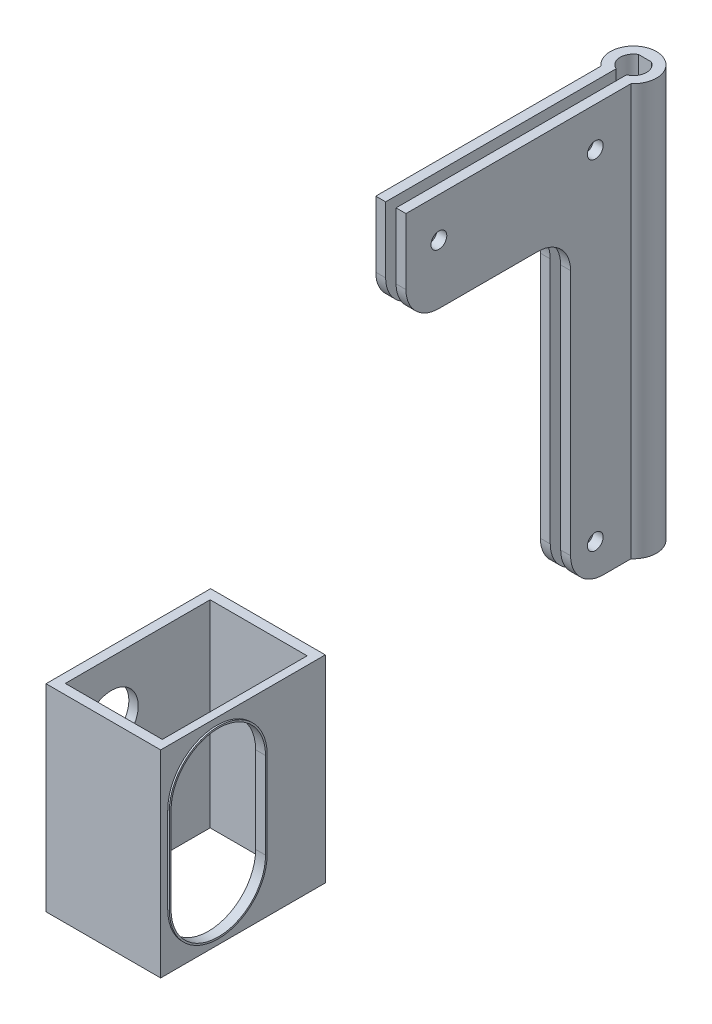
SolidWorks part; units mm, degrees
ref_plane "Front Plane" through (0, 0, 0) normal (0, 0, 1) x (1, 0, 0)
ref_plane "Top Plane" through (0, 0, 0) normal (0, 1, 0) x (1, 0, 0)
ref_plane "Right Plane" through (0, 0, 0) normal (1, 0, 0) x (0, 0, -1)
ref_plane "ULTRASONIC CENTER" through (0, 0, 125) normal (0, 0, 1) x (1, 0, 0)
sketch "Sketch1" plane through (0, 0, 0) normal (0, 1, 0) x (1, 0, 0)
  line L0 (-1.5875, -3.6715) -> (-1.5875, -23.6715)
  line L1 (1.5875, -3.6715) -> (1.5875, -23.6715)
  line L2 (1.9365, 3.5) -> (-1.9365, 3.5)
  line L3 (4.5875, -5.2872) -> (4.5875, -23.6715)
  line L4 (-4.5875, -5.2872) -> (-4.5875, -23.6715)
  line L5 (-4.5875, -23.6715) -> (-1.5875, -23.6715)
  line L6 (1.5875, -23.6715) -> (4.5875, -23.6715)
  arc A0 (1.5875, -3.6715) -> (1.9365, 3.5) centre (0, 0) ccw
  arc A1 (4.5875, -5.2872) -> (-4.5875, -5.2872) centre (0, 0) ccw
  arc A2 (-1.9365, 3.5) -> (-1.5875, -3.6715) centre (0, 0) ccw
  arc A4 (1.5875, -3.6715) -> (-1.5875, -3.6715) centre (0, 0) ccw construction
  dimension "D1" = 4
  dimension "D2" = 20
  dimension "D3" = 3.5
  dimension "D5" = 3.175
  dimension "D4" = 3
extrude "Boss-Extrude1" add sketch "Sketch1" along normal blind 125
ref_plane "PADDLE CENTER" through (0, 0, 0) normal (-1, 0, 0) x (0, 0, 1)
ref_plane "DISC CENTER" through (0, -15, 0) normal (0, 1, 0) x (1, 0, 0)
ref_axis "Axis1" through (0, -15, 24.6715) along (0, 0, -1)
ref_plane "OFFSET" through (-36.4125, 0, 0) normal (-1, 0, 0) x (0, 0, 1)
ref_plane "PADDLE SURFACE" through (-1.5875, 0, 0) normal (1, 0, 0) x (0, 0, -1)
ref_axis "Axis2" through (-36.4125, -15, -8.5336) along (0, 0, 1)
ref_point "ULTRASONIC"
sketch "Sketch5" plane through (0, 125, 0) normal (0, 1, 0) x (1, 0, 0)
  line L1 (-1.5875, -111.5) -> (-1.5875, -106.5)
  line L2 (-47.5875, -106.5) -> (-47.5875, -141.5)
  line L3 (-47.5875, -141.5) -> (-1.5875, -141.5)
  line L4 (-1.5875, -141.5) -> (-1.5875, -136.5)
  line L5 (-1.5875, -136.5) -> (-42.5875, -136.5)
  line L9 (-1.5875, -23.6715) -> (-1.5875, -3.6715) construction
  line L10 (-42.5875, -111.5) -> (-1.5875, -111.5)
  line L12 (-42.5875, -136.5) -> (-42.5875, -111.5)
  line L13 (-47.5875, -106.5) -> (-1.5875, -106.5)
  line L18 (-18.6703, -4) -> (17.7565, -4) construction
  circle A0 centre (0, 0) radius 4 construction
  arc A1 (-1.9365, 3.5) -> (-1.5875, -3.6715) centre (0, 0) ccw construction
  point P2 (-42.5875, -124)
  dimension "D2" = 120
  dimension "D1" = 41
  dimension "D3" = 25
  dimension "D4" = 5
  dimension "D5" = 5
  dimension "D7" = 5
extrude "Boss-Extrude2" [suppressed] add sketch "Sketch5" against normal mid plane 30 from offset 137.5 offset against normal yes
sketch "Sketch6" plane through (0, 125, 0) normal (0, 1, 0) x (1, 0, 0)
  line L0 (4.5875, -23.6715) -> (4.5875, -5.2872) construction
  line L1 (1.5875, -23.6715) -> (4.5875, -23.6715)
  line L2 (1.5875, -23.6715) -> (1.5875, -73.6715)
  line L3 (1.5875, -73.6715) -> (4.5875, -73.6715)
  line L4 (4.5875, -23.6715) -> (4.5875, -73.6715)
  line L6 (-1.5875, -23.6715) -> (-1.5875, -3.6715) construction
  line L7 (-4.5875, -23.6715) -> (-1.5875, -23.6715)
  line L8 (-4.5875, -23.6715) -> (-4.5875, -73.6715)
  line L9 (-4.5875, -73.6715) -> (-1.5875, -73.6715)
  line L10 (-1.5875, -23.6715) -> (-1.5875, -73.6715)
  dimension "D1" = 50
extrude "Boss-Extrude3" add sketch "Sketch6" against normal blind 30
fillet "Fillet6" radius 10 6 edges at (3.0875, 0, 23.6715) (-3.0875, 0, 23.6715) (3.0875, 95, 73.6715) (-3.0875, 95, 73.6715) (3.0875, 95, 23.6715) (-3.0875, 95, 23.6715)
hole_wizard "M4 Clearance Hole1" positions "Sketch2" profile "Sketch3" hole size "M4" standard "ANSI Metric" end condition through all
sketch "Sketch2" plane through (4.5875, 0, 0) normal (1, 0, 0) x (0, 0, -1)
  line L4 (-73.6715, 125) -> (-5.2872, 125) construction
  line L6 (-73.6715, 105) -> (-73.6715, 125) construction
  point P0 (-16.1715, 113)
  point P4 (-16.1715, 10)
  point P19 (-63.6715, 113)
  dimension "D1" = 103
  dimension "D2" = 12
  dimension "D3" = 47.5
  dimension "D4" = 10
sketch "Sketch3" plane through (4.5875, 113, 16.1715) normal (0, 1, 0) x (0, 0, -1)
  line L0 (0, 0) -> (0, 11.5875)
  line L1 (0, 11.5875) -> (2.4, 11.5875)
  line L2 (2.4, 11.5875) -> (2.4, 0)
  line L5 (2.4, 0) -> (0, 0)
  line L11 (0, -6.35) -> (0, 107.95) construction
  dimension "Thru Hole Dia." = 4.8
  dimension "Thru Hole Depth" = 11.5875
sketch "Sketch9" [suppressed] plane through (-1.5875, 0, 0) normal (1, 0, 0) x (0, 0, -1)
  line L0 (-105.675, 2.5) -> (-22.7496, 2.5)
  line L1 (-105.675, 2.5) -> (-105.675, -27.5)
  line L2 (-105.675, -27.5) -> (-22.7496, -27.5)
  line L3 (-22.7496, 95) -> (-22.7496, 0) construction
  line L5 (-4.1335, 0) -> (-4.1335, -27.5)
  line L6 (-4.1335, -27.5) -> (-22.7496, -27.5)
  line L7 (-22.7496, 2.5) -> (-22.7496, 0)
  line L8 (-22.7496, 95) -> (-22.7496, 0) construction
  line L9 (-22.7496, 0) -> (-4.1335, 0) construction
  line L10 (-22.7496, 0) -> (-4.1335, 0)
extrude "Boss-Extrude5" [suppressed] add sketch "Sketch9" against normal up to surface (3 mm away)
chamfer "Chamfer2" [suppressed] distance 42 distance2 35
fillet "Fillet1" [suppressed] radius 40
fillet "Fillet2" [suppressed] radius 10
sketch "Sketch11" plane through (0, 125, 0) normal (0, 1, 0) x (1, 0, 0)
  line L0 (-21.2191, -4) -> (29.064, -4) construction
  line L1 (4.5875, -66.5) -> (47.5875, -66.5)
  line L2 (4.5875, -73.6715) -> (4.5875, -5.2872) construction
  line L3 (47.5875, -66.5) -> (47.5875, -101.5)
  line L4 (47.5875, -101.5) -> (4.5875, -101.5)
  line L5 (4.5875, -101.5) -> (4.5875, -96.5)
  line L6 (4.5875, -96.5) -> (42.5875, -96.5)
  line L7 (42.5875, -96.5) -> (42.5875, -71.5)
  line L8 (42.5875, -71.5) -> (4.5875, -71.5)
  line L9 (4.5875, -71.5) -> (4.5875, -66.5)
  line L10 (1.5875, -3.6715) -> (1.5875, -73.6715) construction
  circle A0 centre (0, 0) radius 4 construction
  arc A1 (-1.9365, 3.5) -> (-1.5875, -3.6715) centre (0, 0) ccw construction
  point P17 (42.5875, -84)
  dimension "D1" = 5
  dimension "D2" = 5
  dimension "D3" = 5
  dimension "D4" = 41
  dimension "D5" = 80
  dimension "D6" = 25
extrude "Boss-Extrude6" [suppressed] add sketch "Sketch11" along normal mid plane 30 from offset 137.5 offset against normal yes
sketch "Sketch13" [suppressed] plane through (4.5875, 0, 0) normal (-1, 0, 0) x (0, 0, 1)
  line L0 (70.675, 2.5) -> (22.7496, 2.5)
  line L1 (22.7496, 55) -> (22.7496, 42.5) construction
  line L2 (22.7496, 2.5) -> (22.7496, 0)
  line L3 (22.7496, 0) -> (4.1335, 0)
  line L4 (70.675, 2.5) -> (70.675, -27.5)
  line L5 (70.675, -27.5) -> (4.1335, -27.5)
  line L6 (4.1335, -27.5) -> (4.1335, 0)
extrude "Boss-Extrude8" [suppressed] add sketch "Sketch13" along normal up to surface (3 mm away)
chamfer "Chamfer3" [suppressed] distance 42 distance2 35
fillet "Fillet5" [suppressed] radius 40
fillet "Fillet4" [suppressed] radius 10
sketch "Sketch14" [suppressed] plane through (0, 0, 110.675) normal (0, 0, 1) x (1, 0, 0)
  line L5 (-47.5875, -27.5) -> (-47.5875, 2.5) construction
  line L6 (-40.0875, -7.5) -> (-40.0875, -17.5) construction
  line L7 (-37.5875, -7.5) -> (-37.5875, -17.5)
  line L8 (-42.5875, -7.5) -> (-42.5875, -17.5)
  line L9 (-42.5875, -27.5) -> (-42.5875, 2.5) construction
  arc A0 (-37.5875, -7.5) -> (-42.5875, -7.5) centre (-40.0875, -7.5) ccw
  arc A1 (-42.5875, -17.5) -> (-37.5875, -17.5) centre (-40.0875, -17.5) ccw
  point P2 (-40.0875, -12.5)
  point P9 (-47.5875, -12.5)
  dimension "D1" = 5
  dimension "D2" = 10
extrude "Cut-Extrude1" [suppressed] cut sketch "Sketch14" against normal up to next
sketch "Sketch15" [suppressed] plane through (0, 0, 70.675) normal (0, 0, 1) x (1, 0, 0)
  line L0 (40.0875, -7.5) -> (40.0875, -17.5) construction
  line L1 (42.5875, -7.5) -> (42.5875, -17.5)
  line L2 (37.5875, -7.5) -> (37.5875, -17.5)
  line L3 (42.5875, 2.5) -> (42.5875, -27.5) construction
  arc A0 (42.5875, -7.5) -> (37.5875, -7.5) centre (40.0875, -7.5) ccw
  arc A1 (37.5875, -17.5) -> (42.5875, -17.5) centre (40.0875, -17.5) ccw
  point P2 (40.0875, -12.5)
  point P9 (42.5875, -12.5)
  dimension "D1" = 5
  dimension "D2" = 10
extrude "Cut-Extrude2" [suppressed] cut sketch "Sketch15" against normal up to next
sketch "Sketch16" plane through (-36.4125, 0, 0) normal (-1, 0, 0) x (0, 0, 1)
  line L0 (125, 15) -> (125, -45) construction
  line L1 (92, 15) -> (142, 15)
  line L3 (92, -45) -> (142, -45)
  line L4 (142, 15) -> (142, -45)
  line L5 (92, 15) -> (142, -45) construction
  line L6 (92, -45) -> (142, 15) construction
  line L7 (132.5, -11) -> (132.5, -19) construction
  line L12 (92, 15) -> (92, -45)
  line L13 (134.75, -11) -> (134.75, -19)
  line L14 (130.25, -11) -> (130.25, -19)
  line L15 (116.35, -10) -> (116.35, -20) construction
  line L16 (117.35, -10) -> (117.35, -20)
  line L17 (115.35, -10) -> (115.35, -20)
  circle A0 centre (125, -2) radius 8.15
  circle A1 centre (125, -28) radius 8.15
  arc A4 (134.75, -11) -> (130.25, -11) centre (132.5, -11) ccw
  arc A5 (130.25, -19) -> (134.75, -19) centre (132.5, -19) ccw
  arc A6 (117.35, -10) -> (115.35, -10) centre (116.35, -10) ccw
  arc A7 (115.35, -20) -> (117.35, -20) centre (116.35, -20) ccw
  point P1 (117, -15)
  point P14 (125, -15)
  point P15 (132.5, -15)
  point P26 (116.35, -15)
  dimension "D4" = 16.3
  dimension "D5" = 16.3
  dimension "D1" = 60
  dimension "D3" = 50
  dimension "D6" = 26
  dimension "D7" = 13
  dimension "D2" = 17
  dimension "D8" = 7.5
  dimension "D10" = 4.5
  dimension "D11" = 8
  dimension "D12" = 8.65
  dimension "D13" = 2
  dimension "D14" = 10
extrude "Boss-Extrude9" add sketch "Sketch16" against normal blind 2.85 separate body contours L3 L4 L1 L12 A1 A0 region at (-36.4125, 14.219, 117)
sketch "Sketch19" plane through (-33.5625, 0, 0) normal (1, 0, 0) x (0, 0, -1)
  line L0 (-92, -45) -> (-142, -45) construction
  line L9 (-142, 15) -> (-139.5, 15)
  line L10 (-142, 15) -> (-142, -45)
  line L11 (-142, -45) -> (-139.5, -45)
  line L12 (-139.5, 15) -> (-139.5, -45)
  line L13 (-92, 15) -> (-142, 15) construction
  line L14 (-92, -45) -> (-94.5, -45)
  line L15 (-92, -45) -> (-92, 15)
  line L16 (-92, 15) -> (-94.5, 15)
  line L17 (-94.5, -45) -> (-94.5, 15)
  dimension "D1" = 2.5
  dimension "D2" = 2.5
extrude "Boss-Extrude11" add sketch "Sketch19" along normal up to surface (31.975 mm away) up to plane "PADDLE SURFACE"
sketch "Sketch20" plane through (0, -45, 0) normal (0, -1, 0) x (1, 0, 0)
  line L0 (-1.5875, 92) -> (-36.4125, 92) construction
  line L1 (-1.5875, 142) -> (-4.0875, 142)
  line L2 (-1.5875, 142) -> (-1.5875, 92)
  line L3 (-1.5875, 92) -> (-4.0875, 92)
  line L4 (-4.0875, 142) -> (-4.0875, 92)
  dimension "D1" = 2.5
extrude "Boss-Extrude12" add sketch "Sketch20" against normal up to surface (60 mm away) up to face at (-18.2875, 15, 117)
sketch "Sketch21" plane through (-1.5875, 0, 0) normal (1, 0, 0) x (0, 0, -1)
  line L0 (-125, -1.9) -> (-125, -28.1) construction
  line L1 (-125, 55) -> (-125, -55) construction
  line L2 (-110, -1.9) -> (-110, -28.1) construction
  line L3 (-140, -1.9) -> (-140, -28.1) construction
  line L4 (-110.15, -1.9) -> (-110.15, -28.1)
  line L5 (-139.85, -1.9) -> (-139.85, -28.1)
  line L6 (-110.65, -1.9) -> (-110.65, -28.1)
  line L7 (-139.35, -1.9) -> (-139.35, -28.1)
  arc A0 (-110, -1.9) -> (-140, -1.9) centre (-125, -1.9) ccw construction
  arc A1 (-140, -28.1) -> (-110, -28.1) centre (-125, -28.1) ccw construction
  arc A2 (-139.85, -28.1) -> (-110.15, -28.1) centre (-125, -28.1) ccw
  arc A3 (-110.15, -1.9) -> (-139.85, -1.9) centre (-125, -1.9) ccw
  arc A4 (-139.35, -28.1) -> (-110.65, -28.1) centre (-125, -28.1) ccw
  arc A5 (-110.65, -1.9) -> (-139.35, -1.9) centre (-125, -1.9) ccw
  point P5 (-125, -15)
  dimension "D1" = 26.2
  dimension "D2" = 30
  dimension "D3" = 0.15
  dimension "D4" = 0.5
extrude "Cut-Extrude3" cut sketch "Sketch21<2>" against normal up to next (2.5 mm away) contours L6 A5 L7 A4 region at (-1.5875, -15, 125)
sketch "Sketch21<2>" plane through (-1.5875, 0, 0) normal (1, 0, 0) x (0, 0, -1) same geometry as "Sketch21"
extrude "Boss-Extrude13" add sketch "Sketch21" along normal blind 0.5
sketch "Sketch18" plane through (0, -45, 0) normal (0, -1, 0) x (1, 0, 0)
  line L0 (-1.5875, -68.75) -> (-1.5875, 68.75) construction
  line L1 (-36.4125, 142) -> (-1.5875, 142)
  line L2 (-36.4125, 142) -> (-36.4125, 139)
  line L3 (-36.4125, 139) -> (-1.5875, 139)
  line L4 (-1.5875, 142) -> (-1.5875, 139)
  line L6 (-36.4125, 92) -> (-1.5875, 92)
  line L7 (-36.4125, 92) -> (-36.4125, 95)
  line L8 (-36.4125, 95) -> (-1.5875, 95)
  line L9 (-1.5875, 92) -> (-1.5875, 95)
  dimension "D1" = 3
  dimension "D2" = 3
extrude "Boss-Extrude10" add sketch "Sketch18" against normal up to surface (60 mm away) up to face at (-18.825, 15, 117)
equation "\"D7@Sketch16\"=\"D6@Sketch16\"/2"
